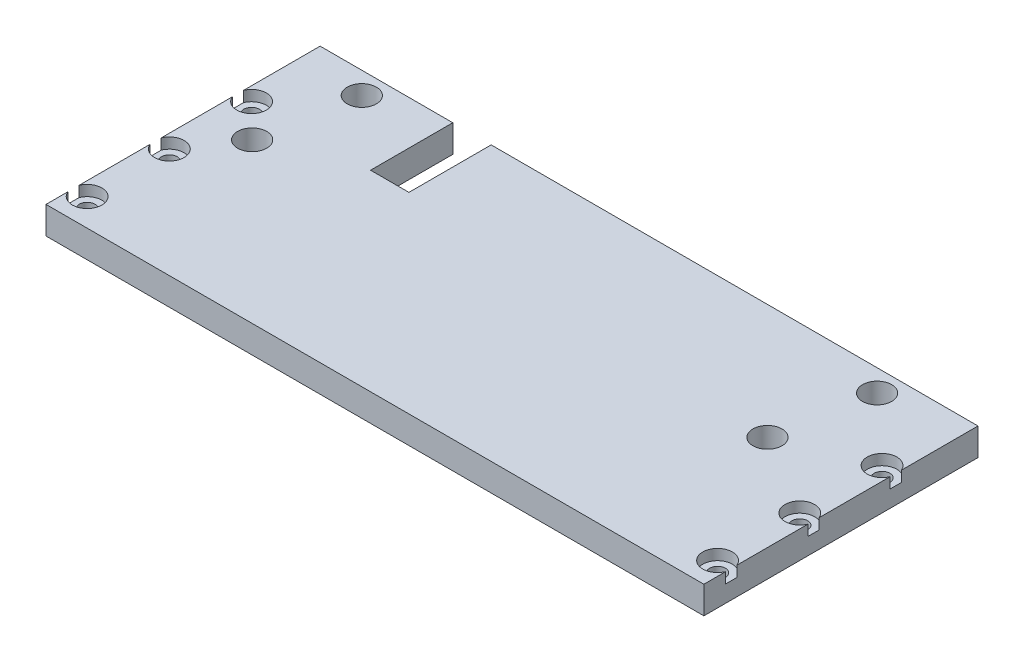
SolidWorks part; units mm, degrees
ref_plane "Front Plane" through (0, 0, 0) normal (0, 0, 1) x (1, 0, 0)
ref_plane "Top Plane" through (0, 0, 0) normal (0, 1, 0) x (1, 0, 0)
ref_plane "Right Plane" through (0, 0, 0) normal (1, 0, 0) x (0, 0, -1)
sketch "Sketch1" plane through (0, 0, 0) normal (0, 1, 0) x (1, 0, 0)
  line L1 (0, 0) -> (-152.4, 0)
  line L2 (0, 0) -> (0, 63.5)
  line L3 (0, 63.5) -> (-152.4, 63.5)
  line L4 (-152.4, 0) -> (-152.4, 63.5)
  dimension "D1" = 63.5
  dimension "D2" = 152.4
extrude "Boss-Extrude1" add sketch "Sketch1" along normal blind 6.35
sketch "Sketch2" plane through (0, 6.35, 0) normal (0, 1, 0) x (1, 0, 0)
  line L1 (0, 0) -> (0, 63.5) construction
  line L2 (-152.4, 63.5) -> (-152.4, 0) construction
  line L3 (-152.4, 0) -> (0, 0) construction
  circle A0 centre (-149.225, 44.45) radius 1.8288
  circle A1 centre (-149.225, 25.4) radius 1.8288
  circle A2 centre (-149.225, 6.35) radius 1.8288
  circle A3 centre (-3.175, 25.4) radius 1.8288
  circle A4 centre (-3.175, 44.45) radius 1.8288
  circle A5 centre (-3.175, 6.35) radius 1.8288
  dimension "D10" = 3.6576
  dimension "D11" = 3.6576
  dimension "D12" = 3.6576
  dimension "D13" = 3.6576
  dimension "D14" = 3.6576
  dimension "D15" = 3.6576
  dimension "D16" = 3.175
  dimension "D17" = 3.175
  dimension "D18" = 3.175
  dimension "D2" = 6.35
  dimension "D3" = 25.4
  dimension "D19" = 44.45
  dimension "D4" = 6.35
  dimension "D5" = 25.4
  dimension "D6" = 44.45
  dimension "D7" = 3.175
  dimension "D8" = 3.175
  dimension "D9" = 3.175
sketch "Sketch5" plane through (0, 6.35, 0) normal (0, 1, 0) x (1, 0, 0)
  line L0 (-121.666, 63.5) -> (-121.666, 44.45)
  line L1 (0, 63.5) -> (-152.4, 63.5) construction
  line L2 (-121.666, 44.45) -> (-112.776, 44.45)
  line L3 (-112.776, 44.45) -> (-112.776, 63.5)
  line L5 (-152.4, 63.5) -> (-152.4, 0) construction
  line L6 (-121.666, 63.5) -> (-112.776, 63.5)
  dimension "D1" = 39.624
  dimension "D2" = 8.89
  dimension "D3" = 19.05
extrude "Cut-Extrude2" cut sketch "Sketch5" against normal through all
sketch "Sketch6" plane through (0, 6.35, 0) normal (0, 1, 0) x (1, 0, 0)
  line L0 (-152.4, 63.5) -> (-152.4, 0) construction
  line L1 (-121.666, 63.5) -> (-152.4, 63.5) construction
  circle A0 centre (-137.668, 58.42) radius 3.3782
  dimension "D2" = 5.08
  dimension "D3" = 6.7564
  dimension "D1" = 14.732
sketch "Sketch13" plane through (0, 6.35, 0) normal (0, 1, 0) x (1, 0, 0)
  line L0 (0, 0) -> (0, 63.5) construction
  line L1 (0, 63.5) -> (-112.776, 63.5) construction
  circle A0 centre (-22.098, 36.83) radius 3.3782
  circle A1 centre (-18.288, 58.42) radius 3.3782
  dimension "D1" = 18.288
  dimension "D2" = 22.098
  dimension "D3" = 6.7564
  dimension "D4" = 6.7564
  dimension "D5" = 21.59
  dimension "D6" = 5.08
sketch "Sketch16" plane through (0, 6.35, 0) normal (0, 1, 0) x (1, 0, 0)
  line L0 (-152.4, 63.5) -> (-152.4, 0) construction
  circle A0 centre (-141.478, 36.83) radius 3.3782
  circle A1 centre (-137.668, 58.42) radius 3.3782 construction
  dimension "D1" = 21.59
  dimension "D2" = 10.922
extrude "Cut-Extrude3" cut sketch "Sketch16" against normal through all contours A0
extrude "Cut-Extrude4" cut sketch "Sketch6" against normal through all contours A0
extrude "Cut-Extrude5" cut sketch "Sketch13" against normal through all
sketch "Sketch25" plane through (0, 6.35, 0) normal (0, 1, 0) x (1, 0, 0)
  circle A0 centre (-149.225, 44.45) radius 3.429
  circle A1 centre (-149.225, 25.4) radius 3.429
  circle A2 centre (-149.225, 6.35) radius 3.429
  circle A3 centre (-3.175, 44.45) radius 3.429
  circle A4 centre (-3.175, 25.4) radius 3.429
  circle A5 centre (-3.175, 6.35) radius 3.429
  dimension "D1" = 6.858
  dimension "D2" = 6.858
  dimension "D3" = 6.858
  dimension "D4" = 6.858
  dimension "D5" = 6.858
extrude "Cut-Extrude6" cut sketch "Sketch25" against normal blind 2.4638
extrude "Cut-Extrude7" cut sketch "Sketch2" against normal blind 6.35
